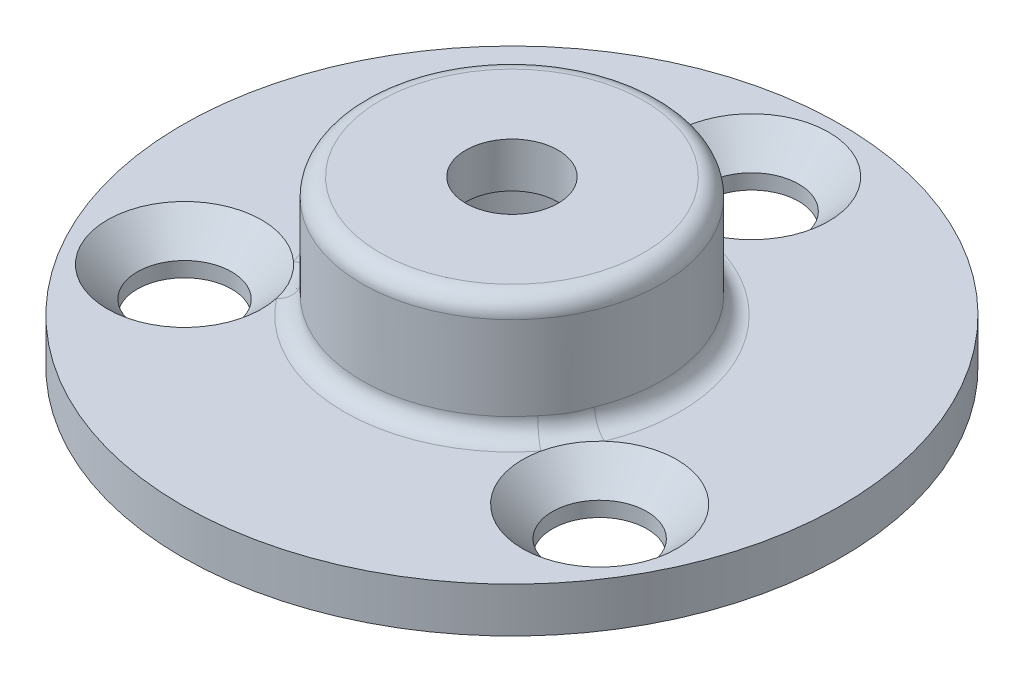
SolidWorks part; units mm, degrees
ref_plane "Front Plane" through (0, 0, 0) normal (0, 0, 1) x (1, 0, 0)
ref_plane "Top Plane" through (0, 0, 0) normal (0, 1, 0) x (1, 0, 0)
ref_plane "Right Plane" through (0, 0, 0) normal (1, 0, 0) x (0, 0, -1)
sketch "Sketch1" plane through (0, 0, 0) normal (0, 1, 0) x (1, 0, 0)
  circle A0 centre (0, 0) radius 11
  dimension "D1" = 22
extrude "Boss-Extrude1" add sketch "Sketch1" along normal blind 1.5
sketch "Sketch2" plane through (0, 1.5, 0) normal (0, 1, 0) x (1, 0, 0)
  circle A0 centre (0, 0) radius 5
  dimension "D1" = 10
extrude "Boss-Extrude2" add sketch "Sketch2" along normal blind 4
sketch "Sketch3" plane through (0, 0, 0) normal (0, -1, 0) x (1, 0, 0)
  circle A0 centre (0, 0) radius 3.75
  dimension "D1" = 7.5
extrude "Cut-Extrude1" cut sketch "Sketch3" against normal blind 4
sketch "Sketch4" plane through (0, 5.5, 0) normal (0, 1, 0) x (1, 0, 0)
  circle A0 centre (0, 0) radius 1.54
  dimension "D1" = 3.08
extrude "Cut-Extrude2" cut sketch "Sketch4" against normal through all
sketch "Sketch5" plane through (0, 1.5, 0) normal (0, 1, 0) x (1, 0, 0)
  line L0 (0, 0) -> (0, 8) construction
  circle A0 centre (0, 8) radius 1.575
  circle A2 centre (0, 0) radius 11 construction
  circle A3 centre (0, 0) radius 5 construction
  circle A4 centre (0, 0) radius 11 construction
  circle A5 centre (0, 0) radius 5 construction
  circle A6 centre (6.9282, -4) radius 1.575
  circle A7 centre (-6.9282, -4) radius 1.575
  point P16 (0, 0)
  dimension "D1" = 8
  dimension "D2" = 3.15
  dimension "D3" = 3
extrude "Cut-Extrude3" cut sketch "Sketch5" against normal through all
chamfer "Chamfer1" distance 1 angle 45 3 edges at (6.9282, 1.5, 5.575) (-6.9282, 1.5, 5.575) (0, 1.5, -6.425)
fillet "Fillet1" radius 0.6 2 edges at (0, 5.5, 5) (0, 1.5, 5)
